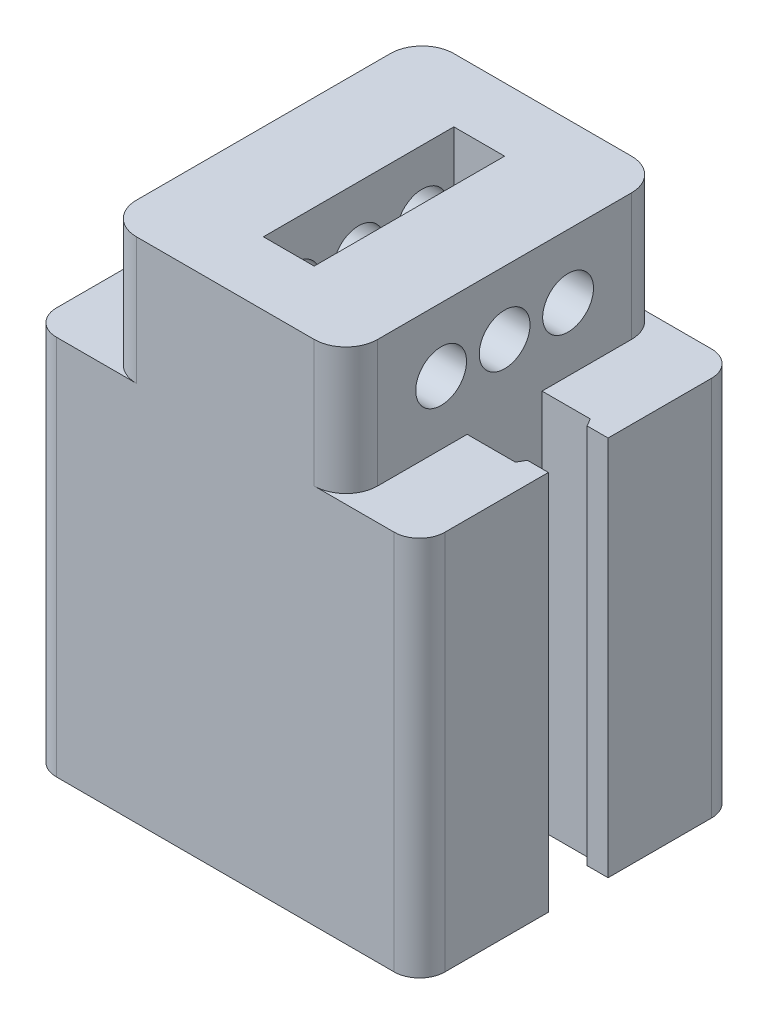
SolidWorks part; units mm, degrees
ref_plane "Front Plane" through (0, 0, 0) normal (0, 0, 1) x (1, 0, 0)
ref_plane "Top Plane" through (0, 0, 0) normal (0, 1, 0) x (1, 0, 0)
ref_plane "Right Plane" through (0, 0, 0) normal (1, 0, 0) x (0, 0, -1)
sketch "Sketch2" plane through (0, 0, 0) normal (0, 1, 0) x (1, 0, 0)
  line L0 (-13.3, 12.5) -> (13.3, 12.5)
  line L1 (-13.3, -12.5) -> (13.3, -12.5)
  line L2 (-9.5, 2.95) -> (-9.5, -2.95)
  line L3 (-9.5, -2.95) -> (-13.3, -2.95)
  line L4 (-13.3, -2.95) -> (-13.6464, -2.35)
  line L5 (-13.6464, -2.35) -> (-15.3, -2.35)
  line L6 (-9.5, 2.95) -> (-13.3, 2.95)
  line L7 (-13.3, 2.95) -> (-13.6464, 2.35)
  line L8 (-13.6464, 2.35) -> (-15.3, 2.35)
  line L9 (9.5, 2.95) -> (13.3, 2.95)
  line L10 (13.3, 2.95) -> (13.6464, 2.35)
  line L11 (13.6464, 2.35) -> (15.3, 2.35)
  line L12 (9.5, -2.95) -> (13.3, -2.95)
  line L13 (13.3, -2.95) -> (13.6464, -2.35)
  line L14 (13.6464, -2.35) -> (15.3, -2.35)
  line L15 (9.5, -2.95) -> (9.5, 2.95)
  line L16 (-9.5, 2.95) -> (-9.5, -2.95)
  line L17 (15.3, 10.5) -> (15.3, 2.35)
  line L18 (15.3, -10.5) -> (15.3, -2.35)
  line L19 (-15.3, -10.5) -> (-15.3, -2.35)
  line L20 (-15.3, 10.5) -> (-15.3, 2.35)
  line L21 (0, 12.5) -> (0, -12.5) construction
  line L22 (-15.3, 0) -> (15.3, 0) construction
  arc A0 (-15.3, -10.5) -> (-13.3, -12.5) centre (-13.3, -10.5) ccw
  arc A1 (13.3, -12.5) -> (15.3, -10.5) centre (13.3, -10.5) ccw
  arc A2 (15.3, 10.5) -> (13.3, 12.5) centre (13.3, 10.5) ccw
  arc A3 (-13.3, 12.5) -> (-15.3, 10.5) centre (-13.3, 10.5) ccw
  point P22 (-15.3, -12.5)
  point P31 (0, 0)
  dimension "D1" = 2
  dimension "D2" = 2.95
  dimension "D3" = 25
  dimension "D4" = 30.6
  dimension "D5" = 30.6
  dimension "D6" = 2.95
  dimension "D7" = 2.95
  dimension "D8" = 2.95
extrude "Boss-Extrude1" add sketch "Sketch2" along normal blind 30 contours L21 L0 A3 L20 L8 L7 L6 L2 L3 L4 L5 L19 A0 L1 | L0 L21 L1 A1 L18 L14 L13 L12 L15 L9 L10 L11 L17 A2 region at (-7.1908, 0, 0) region at (7.1908, 0, 0)
sketch "Sketch3" plane through (0, 30, 0) normal (0, 1, 0) x (1, 0, 0)
  line L0 (-9.5, 0) -> (-9.5, -10)
  line L1 (-9.5, 2.95) -> (-9.5, -2.95) construction
  line L2 (-13.3, -12.5) -> (13.3, -12.5) construction
  line L3 (-9.5, 10) -> (-9.5, 0)
  line L4 (-13.3, 12.5) -> (13.3, 12.5) construction
  line L5 (0, 12.5) -> (0, -12.5) construction
  line L6 (9.5, 0) -> (9.5, -10)
  line L7 (9.5, 10) -> (9.5, 0)
  line L8 (-7, 12.5) -> (7, 12.5)
  line L9 (7, -12.5) -> (-7, -12.5)
  line L10 (-9.5, 0) -> (9.5, 0) construction
  line L12 (-2, -7.5) -> (2, -7.5)
  line L13 (-2, -7.5) -> (-2, 7.5)
  line L14 (-2, 7.5) -> (2, 7.5)
  line L15 (2, -7.5) -> (2, 7.5)
  line L16 (-2, -7.5) -> (2, 7.5) construction
  line L17 (-2, 7.5) -> (2, -7.5) construction
  line L18 (-4, -9.5) -> (4, -9.5)
  line L19 (-6, -7.5) -> (-6, 7.5)
  line L20 (-4, 9.5) -> (4, 9.5)
  line L21 (6, -7.5) -> (6, 7.5)
  line L22 (-6, -9.5) -> (6, 9.5) construction
  line L23 (-6, 9.5) -> (6, -9.5) construction
  arc A0 (7, -12.5) -> (9.5, -10) centre (7, -10) ccw
  arc A1 (9.5, 10) -> (7, 12.5) centre (7, 10) ccw
  arc A2 (-9.5, 10) -> (-7, 12.5) centre (-7, 10) cw
  arc A3 (-9.5, -10) -> (-7, -12.5) centre (-7, -10) ccw
  arc A4 (4, 9.5) -> (6, 7.5) centre (4, 7.5) cw
  arc A5 (6, -7.5) -> (4, -9.5) centre (4, -7.5) cw
  arc A6 (-4, -9.5) -> (-6, -7.5) centre (-4, -7.5) cw
  arc A7 (-6, 7.5) -> (-4, 9.5) centre (-4, 7.5) cw
  point P16 (9.5, -12.5)
  point P19 (9.5, 12.5)
  point P22 (-9.5, 12.5)
  point P25 (-9.5, -12.5)
  point P26 (0, 0)
  point P31 (0, 0)
  line M20 (-13.3, -12.5) -> (13.3, -12.5)
  line M26 (9.5, -2.95) -> (9.5, 2.95)
  line M32 (13.3, 12.5) -> (-13.3, 12.5)
  line M38 (-9.5, 2.95) -> (-9.5, -2.95)
  dimension "D1" = 2.5
  dimension "D6" = 2
  dimension "D2" = 4
  dimension "D3" = 15
  dimension "D4" = 4
  dimension "D5" = 2
extrude "Boss-Extrude2" add sketch "Sketch3" along normal blind 10 contours L0 A3 A0 L6 L7 A1 A2 L3 L19 A7 L20 A4 L21 A5 L18 A6 M20 M26 M32 M38 | A7 L19 A6 L18 A5 L21 A4 L20 L15 L12 L13 L14 region at (-9.186, 30, -1.475) region at (-5.2553, 30, 8.7553)
sketch "Sketch4" plane through (0, 40, 0) normal (0, 1, 0) x (1, 0, 0)
  line L1 (-2, -7.5) -> (2, -7.5)
  line L2 (-2, -7.5) -> (-2, 7.5)
  line L3 (-2, 7.5) -> (2, 7.5)
  line L4 (2, -7.5) -> (2, 7.5)
  line L5 (-2, -7.5) -> (2, 7.5) construction
  line L6 (-2, 7.5) -> (2, -7.5) construction
  point P0 (0, 0)
extrude "Cut-Extrude1" cut sketch "Sketch4" against normal blind 35
sketch "Sketch5" plane through (9.5, 0, 0) normal (1, 0, 0) x (0, 0, -1)
  line L0 (-10, 35) -> (10, 35) construction
  line L1 (-10, 40) -> (-10, 30) construction
  line L2 (10, 40) -> (10, 30) construction
  line L3 (0, 35) -> (5, 35) construction
  circle A0 centre (0, 35) radius 2
  circle A1 centre (5, 35) radius 2
  circle A2 centre (0, 35) radius 2
  circle A3 centre (-5, 35) radius 2
  dimension "D1" = 4
  dimension "D4" = 5
  dimension "D2" = 2
  dimension "D3" = 2
extrude "Cut-Extrude2" cut sketch "Sketch5" against normal blind 35 contours A1 | A0 | A3 region at (9.5, 35, 0) region at (9.5, 35, -5) region at (9.5, 35, 5)
